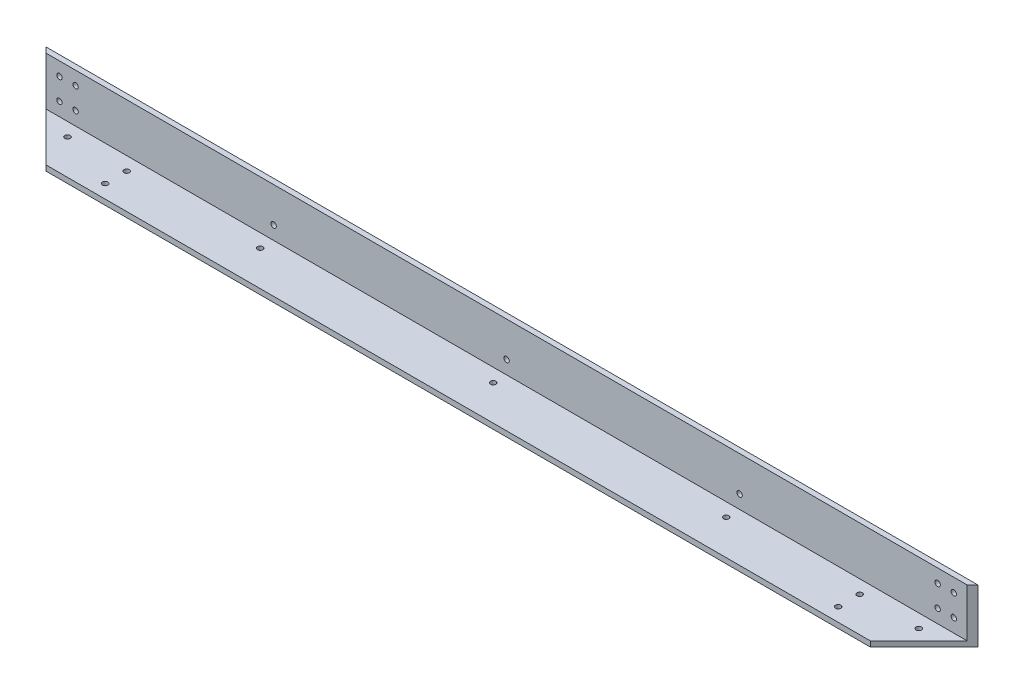
SolidWorks part; units mm, degrees
ref_plane "Front Plane" through (0, 0, 0) normal (0, 0, 1) x (1, 0, 0)
ref_plane "Top Plane" through (0, 0, 0) normal (0, 1, 0) x (1, 0, 0)
ref_plane "Right Plane" through (0, 0, 0) normal (1, 0, 0) x (0, 0, -1)
sketch "Sketch1" plane through (0, 0, 0) normal (1, 0, 0) x (0, 0, -1)
  line L0 (0, 0) -> (-31.75, 0)
  line L1 (-31.75, 0) -> (-31.75, 3.175)
  line L2 (-31.75, 3.175) -> (-3.175, 3.175)
  line L3 (-3.175, 3.175) -> (-3.175, 31.75)
  line L4 (-3.175, 31.75) -> (0, 31.75)
  line L5 (0, 31.75) -> (0, 0)
  dimension "LHeight" = 31.75
  dimension "LWidth" = 31.75
  dimension "LMaterialThickness" = 3.175
  dimension "D1" = 28.575
  dimension "D2" = 28.575
  dimension "D3" = 3.175
extrude "Boss-Extrude1" add sketch "Sketch1" along normal blind 550
chamfer "Chamfer6" distance 31.75 angle 45 1 edges at (550, 1.5875, 31.75)
chamfer "Chamfer7" distance 31.75 angle 45 1 edges at (0, 1.5875, 31.75)
sketch "TopHoles-Sketch3" plane through (0, 3.175, 0) normal (0, 1, 0) x (1, 0, 0)
  line L0 (518.25, -31.75) -> (31.75, -31.75) construction
  line L1 (518.25, -31.75) -> (31.75, -31.75) construction
  line L2 (550, 0) -> (0, 0) construction
  circle A5 centre (58.7375, -23.8125) radius 1.5875
  circle A6 centre (491.2625, -23.8125) radius 1.5875
  circle A9 centre (491.2625, -11.1125) radius 1.5875
  circle A10 centre (58.7375, -11.1125) radius 1.5875
  circle A11 centre (526.1875, -11.1125) radius 1.5875
  circle A12 centre (23.8125, -11.1125) radius 1.5875
  circle A13 centre (275, -11.1125) radius 1.5875
  circle A14 centre (137.5, -11.1125) radius 1.5875
  circle A15 centre (412.5, -11.1125) radius 1.5875
  dimension "D8" = 137.5
  dimension "D10" = 137.5
  dimension "D9" = 3.175
  dimension "D12" = 7.9375
  dimension "D2" = 11.1125
  dimension "D6" = 23.8125
  dimension "D3" = 23.8125
  dimension "D5" = 12.7
  dimension "D4" = 34.925
  dimension "D7" = 34.925
  dimension "D11" = 137.5
extrude "TopHoles-Cut-Extrude2" cut sketch "TopHoles-Sketch3" against normal through all
sketch "LeftHoles-Sketch4" plane through (0, 0, 3.175) normal (0, 0, 1) x (1, 0, 0)
  line L0 (518.25, 0) -> (31.75, 0) construction
  line L3 (550, 31.75) -> (0, 31.75) construction
  line L4 (0, 0) -> (0, 31.75) construction
  line L5 (550, 0) -> (550, 31.75) construction
  circle A1 centre (11.1125, 23.8125) radius 1.5875
  circle A3 centre (529.3625, 23.8125) radius 1.5875
  circle A4 centre (20.6375, 23.8125) radius 1.5875
  circle A5 centre (538.8875, 23.8125) radius 1.5875
  circle A6 centre (11.1125, 11.1125) radius 1.5875
  circle A7 centre (20.6375, 11.1125) radius 1.5875
  circle A8 centre (529.3625, 11.1125) radius 1.5875
  circle A9 centre (538.8875, 11.1125) radius 1.5875
  circle A10 centre (137.5, 11.1125) radius 1.5875
  circle A11 centre (275, 11.1125) radius 1.5875
  circle A12 centre (412.5, 11.1125) radius 1.5875
  dimension "D2" = 3.175
  dimension "D4" = 7.9375
  dimension "D7" = 11.1125
  dimension "D1" = 11.1125
  dimension "D6" = 20.6375
  dimension "D3" = 11.1125
  dimension "D5" = 20.6375
  dimension "D8" = 137.5
  dimension "D9" = 137.5
  dimension "D10" = 137.5
extrude "LeftHoles-Cut-Extrude3" cut sketch "LeftHoles-Sketch4" against normal through all
equation "\"TopRailWidth\"= 1.25in"
equation "\"TopRailHeight\"= 1.25in"
equation "\"RailThickness\"= .125in'Spec"
equation "\"SideRailHoleY1FromEdge\"= \"HoleOffsetFromEdge\""
equation "\"SideRailHoleX1FromSide\"= \"HoleOffsetFromSide\""
equation "\"SideRailLength\"= 550mm"
equation "\"VSWidth\"= 1.25in'Spec"
equation "\"HoleOffsetFromEdge\"= \"RailThickness\" * 2.5"
equation "\"HoleOffsetFromSide\"= \"RailThickness\" * 3.5"
equation "\"TopCBWidth\"= \"TopRailWidth\" - \"RailThickness\"'Equals 28.575"
equation "\"SideRailHoleX2FromSide\"= \"VSWidth\" - \"HoleOffsetFromEdge\" - \"RailThickness\"'Equals 20.6375"
equation "\"FasteningHoleDiameter\"= .125in"
equation "\"SideRailHoleY2FromSide\"= \"HoleOffsetFromSide\""
equation "\"D2@LeftHoles-Sketch4\"=\"FasteningHoleDiameter\""
equation "\"LWidth@Sketch1\"=\"TopRailWidth\""
equation "\"LHeight@Sketch1\"=\"TopRailHeight\""
equation "\"LMaterialThickness@Sketch1\"=\"RailThickness\""
equation "\"D1@Boss-Extrude1\"=\"SideRailLength\""
equation "\"D2@TopHoles-Sketch3\"=\"TopHoleY1FromSide\""
equation "\"D9@TopHoles-Sketch3\" = \"FasteningHoleDiameter\""
equation "\"D4@LeftHoles-Sketch4\"=\"SideRailHoleY1FromEdge\""
equation "\"D1@Chamfer6\"=\"TopRailWidth\""
equation "\"D1@Chamfer7\"=\"TopRailWidth\""
equation "\"D7@LeftHoles-Sketch4\"=\"SideRailHoleY2FromSide\""
equation "\"D1@LeftHoles-Sketch4\"=\"SideRailHoleX1FromSide\""
equation "\"D6@LeftHoles-Sketch4\"=\"SideRailHoleX2FromSide\""
equation "\"D3@LeftHoles-Sketch4\"=\"SideRailHoleX1FromSide\""
equation "\"D5@LeftHoles-Sketch4\"=\"SideRailHoleX2FromSide\""
equation "\"TopHoleY1FromSide\"= \"HoleOffsetFromSide\""
equation "\"TopHoleY2FromY1\"= \"TopCBWidth\" - \"TopHoleY1FromEdge\" - \"HoleOffsetFromEdge\"'Equals 12.7"
equation "\"TopHoleX1FromEdge\"= \"TopCBWidth\" - \"HoleOffsetFromEdge\"'Equals 20.6375"
equation "\"TopHoleX2FromX1\"= \"TopCBLength\" - \"TopHoleX1FromEdge\" - \"HoleOffsetFromEdge\"'Equals 34.925"
equation "\"D5@TopHoles-Sketch3\"=\"TopHoleY2FromY1\""
equation "\"D4@TopHoles-Sketch3\"=\"TopHoleX2FromX1\""
equation "\"D7@TopHoles-Sketch3\"=\"TopHoleX2FromX1\""
equation "\"D3@TopHoles-Sketch3\"=\"TopHoleX1FromEdge\" + \"RailThickness\""
equation "\"D6@TopHoles-Sketch3\"=\"TopHoleX1FromEdge\" + \"RailThickness\""
equation "\"TopCBLength\"= \"TopRailWidth\" * 2'Equals 63.5"
equation "\"TopHoleY1FromEdge\"= \"HoleOffsetFromEdge\""
equation "\"LeftOrRightEnclosureHoleOffsets\"= \"SideRailLength\" / 4"
equation "\"D8@TopHoles-Sketch3\"=\"LeftOrRightEnclosureHoleOffsets\""
equation "\"D10@TopHoles-Sketch3\"=\"LeftOrRightEnclosureHoleOffsets\""
equation "\"D11@TopHoles-Sketch3\"=\"LeftOrRightEnclosureHoleOffsets\""
equation "\"D8@LeftHoles-Sketch4\"=\"LeftOrRightEnclosureHoleOffsets\""
equation "\"D9@LeftHoles-Sketch4\"=\"LeftOrRightEnclosureHoleOffsets\""
equation "\"D10@LeftHoles-Sketch4\"=\"LeftOrRightEnclosureHoleOffsets\""
